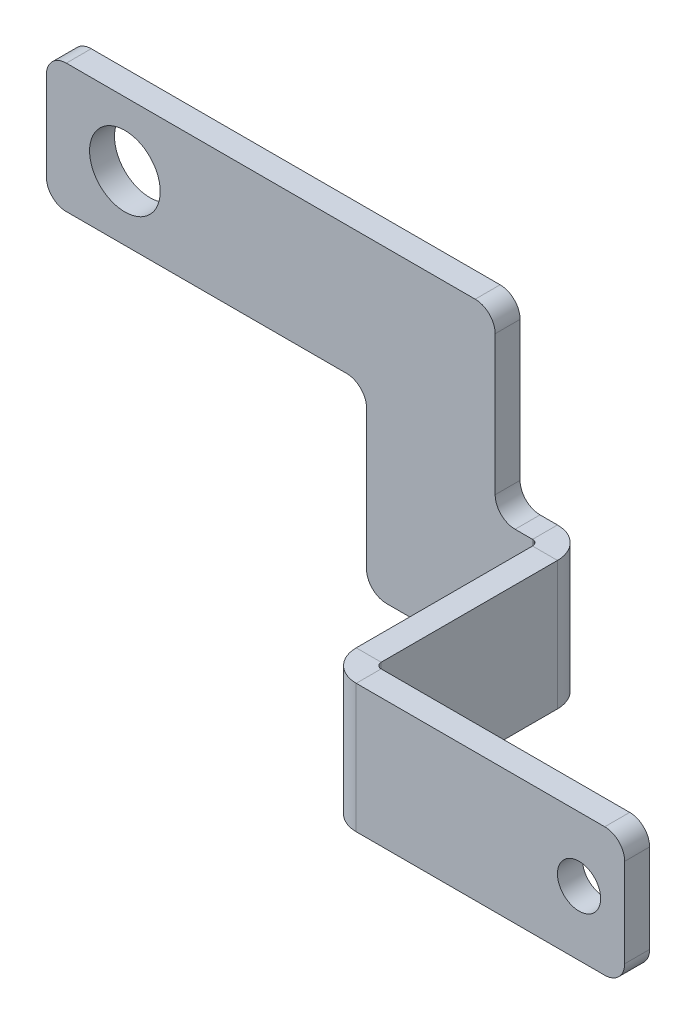
SolidWorks part; units mm, degrees
note: The reader was unsure of these and kept them because the rebuilt part matched: flange length of "Edge-Flange1", "Edge-Flange2".
material "3003-H14"
ref_plane "X-Y Datum" through (0, 0, 0) normal (0, 0, 1) x (1, 0, 0)
ref_plane "X-Z Datum" through (0, 0, 0) normal (0, 1, 0) x (1, 0, 0)
ref_plane "Y-Z Datum" through (0, 0, 0) normal (1, 0, 0) x (0, 0, -1)
sketch "Sketch1" plane through (0, 0, 0) normal (0, 0, 1) x (1, 0, 0)
  line L0 (0, -8.189) -> (57.15, -8.189) construction
  line L1 (0, 0) -> (57.15, 0)
  line L2 (0, 0) -> (0, -16.378)
  line L3 (0, -16.378) -> (40.772, -16.378)
  line L4 (57.15, 0) -> (57.15, -16.378)
  line L5 (61.9125, -31.0236) -> (56.0244, -31.0236) construction
  line L7 (57.15, -16.378) -> (57.15, -22.8346)
  line L8 (57.15, -39.2126) -> (40.772, -39.2126)
  line L9 (40.772, -16.378) -> (40.772, -39.2126)
  line L10 (57.15, -39.2126) -> (61.9125, -39.2126)
  line L12 (57.15, -22.8346) -> (61.9125, -22.8346)
  line L13 (61.9125, -39.2126) -> (61.9125, -22.8346)
  line L14 (88.5359, -31.0236) -> (101.3339, -31.0236) construction
  circle A0 centre (10, -8.189) radius 4 construction
  point P9 (94.9349, -31.0236)
  point P26 (94.9349, -31.0236)
  dimension "D3" = 8
  dimension "D1" = 16.378
  dimension "D2" = 57.15
  dimension "D4" = 10
  dimension "D5" = 4.7625
base flange "Base-Flange1" sketch "Sketch1" thickness 3.175 reverse thickness direction no parameters "D1"=0.7366
hole_wizard "M8 Clearance Hole1" positions "Sketch6" profile "Sketch7" hole size "M8" standard "ANSI Metric" end condition through all
sketch "Sketch6" plane through (0, 0, 0) normal (0, 0, 1) x (1, 0, 0)
  point P0 (10, -8.189)
sketch "Sketch7" plane through (10, -8.189, 0) normal (1, 0, 0) x (0, -1, 0)
  line L0 (0, 0) -> (0, 3.175)
  line L1 (0, 3.175) -> (4.5, 3.175)
  line L2 (4.5, 3.175) -> (4.5, 0)
  line L5 (4.5, 0) -> (0, 0)
  line L11 (0, -6.35) -> (0, 107.95) construction
  dimension "Thru Hole Dia." = 9
  dimension "Thru Hole Depth" = 3.175
edge flange "Edge-Flange1" sketch "Sketch12" flange angle 90 flange length 23.9268 flange position bend outside bend radius 0.7366 thickness 3.175 relief rectangular parameters "D6"=10
sketch "Sketch12" plane through (61.9125, 0, 0) normal (1, 0, 0) x (0, 1, 0)
  line L0 (-39.2126, 0) -> (-22.8346, 0) construction
  line L1 (-39.2126, 0) -> (-22.8346, 0)
  line L2 (-39.2126, 0) -> (-39.2126, 23.9268)
  line L3 (-39.2126, 23.9268) -> (-22.8346, 23.9268)
  line L4 (-22.8346, 23.9268) -> (-22.8346, 0)
bend "EdgeBend1" bend radius 0.7366 bend angle 90 parameters "D5"=1
edge flange "Edge-Flange2" sketch "Sketch15" flange angle 90 flange length 38.1 flange position material outside bend radius 0.7366 thickness 3.175 relief rectangular parameters "D6"=10
sketch "Sketch15" plane through (65.8241, 0, 23.9268) normal (0, 0, 1) x (0, -1, 0)
  line L0 (22.8346, 0) -> (39.2126, 0) construction
  line L1 (22.8346, 0) -> (39.2126, 0)
  line L2 (22.8346, 0) -> (22.8346, 34.925)
  line L3 (22.8346, 34.925) -> (39.2126, 34.925)
  line L4 (39.2126, 34.925) -> (39.2126, 0)
bend "EdgeBend2" bend radius 0.7366 bend angle 90 parameters "D5"=2
sketch "Sketch16" plane through (0, 0, 27.1018) normal (0, 0, 1) x (1, 0, 0)
  point P0 (94.9349, -31.0236)
hole_wizard "M5 Clearance Hole1" positions "Sketch17" profile "Sketch18" hole size "M5" standard "ANSI Metric" end condition through all
sketch "Sketch17" plane through (0, 0, 27.1018) normal (0, 0, 1) x (1, 0, 0)
  point P0 (94.9349, -31.0236)
  point P3 (94.9349, -31.0236)
  point P5 (94.9349, -31.0236)
sketch "Sketch18" plane through (94.9349, -31.0236, 27.1018) normal (1, 0, 0) x (0, -1, 0)
  line L0 (0, 0) -> (0, 30.2768)
  line L1 (0, 30.2768) -> (2.75, 30.2768)
  line L2 (2.75, 30.2768) -> (2.75, 0)
  line L5 (2.75, 0) -> (0, 0)
  line L11 (0, -6.35) -> (0, 107.95) construction
  dimension "Thru Hole Dia." = 5.5
  dimension "Thru Hole Depth" = 30.2768
fillet "Fillet1" radius 2.54 8 edges at (40.772, -16.378, -1.5875) (100.7491, -22.8346, 25.5143) (100.7491, -39.2126, 25.5143) (0, -16.378, -1.5875) (0, 0, -1.5875) (57.15, 0, -1.5875) (57.15, -22.8346, -1.5875) (40.772, -39.2126, -1.5875)
sketch "Bend-Lines1" [suppressed] plane through (0, 0, 0) normal (0, 1, 0) x (1, 0, 0)
sketch "Bounding-Box1" [suppressed] plane through (0, 0, 0) normal (0, 1, 0) x (1, 0, 0)
sheet metal parameters "Sheet-Metal3" thickness 3.175 parameters "D1"=0.7366
flat pattern "Flat-Pattern3" [suppressed]
sketch "Bend-Lines2" plane through (0, 0, 0) normal (0, 1, 0) x (1, 0, 0)
sketch3d "Bounding-Box2" [suppressed]
  line L0 (0, -16.378, 0) -> (-76.2, -16.378, 0) construction
  line L1 (0, 0, 0) -> (-76.2, 0, 0) construction
  line L2 (0, -16.378, 0) -> (0, 0, 0) construction
  line L3 (-76.2, -16.378, 0) -> (-76.2, 0, 0) construction
sheet metal parameters "Sheet-Metal4" thickness 3.175 parameters "D1"=0.7366
flat pattern "Flat-Pattern3"
sketch "Bend-Lines2" plane through (0, 0, 0) normal (0, 1, 0) x (1, 0, 0)
sketch3d "Bounding-Box2" [suppressed]
  line L0 (0, -16.378, 0) -> (76.2, -16.378, 0) construction
  line L1 (0, 0, 0) -> (76.2, 0, 0) construction
  line L2 (0, -16.378, 0) -> (0, 0, 0) construction
  line L3 (76.2, -16.378, 0) -> (76.2, 0, 0) construction
sheet metal parameters "Sheet-Metal5" thickness 3.175 parameters "D1"=0.7366
flat pattern "Flat-Pattern3"
sketch "Bend-Lines2" plane through (0, 0, 0) normal (0, 0, 1) x (1, 0, 0)
  line L0 (62.1503, -45.5626) -> (62.1503, -29.1846) construction
  line L1 (62.1503, -45.5626) -> (62.1503, -29.1846) construction
sketch3d "Bounding-Box2" [suppressed]
  line L0 (0, -45.5626, 0) -> (87.1659, -45.5626, 0) construction
  line L1 (0, 0, 0) -> (87.1659, 0, 0) construction
  line L2 (0, -45.5626, 0) -> (0, 0, 0) construction
  line L3 (87.1659, -45.5626, 0) -> (87.1659, 0, 0) construction
bend of the flat pattern "Flatten-<EdgeBend1>1"
sheet metal parameters "Sheet-Metal6" thickness 3.175 parameters "D1"=0.7366
flat pattern "Flat-Pattern3"
sketch "Bend-Lines2" plane through (0, 0, 0) normal (0, 0, 1) x (1, 0, 0)
  line L0 (62.1503, -45.5626) -> (62.1503, -29.1846) construction
  line L1 (62.1503, -45.5626) -> (62.1503, -29.1846) construction
  line L2 (88.2546, -45.5626) -> (88.2546, -29.1846) construction
  line L3 (88.2546, -45.5626) -> (88.2546, -29.1846) construction
sketch3d "Bounding-Box2" [suppressed]
  line L0 (0, -45.5626, 0) -> (125.5384, -45.5626, 0) construction
  line L1 (0, 0, 0) -> (125.5384, 0, 0) construction
  line L2 (0, -45.5626, 0) -> (0, 0, 0) construction
  line L3 (125.5384, -45.5626, 0) -> (125.5384, 0, 0) construction
bend of the flat pattern "Flatten-<EdgeBend1>1"
bend of the flat pattern "Flatten-<EdgeBend2>1"
sheet metal parameters "Sheet-Metal7" thickness 3.175 parameters "D1"=0.7366
flat pattern "Flat-Pattern3" [suppressed]
sketch "Bend-Lines2" plane through (0, 0, 0) normal (0, 0, 1) x (1, 0, 0)
  line L0 (63.7378, -39.2126) -> (63.7378, -22.8346) construction
  line L1 (63.7378, -39.2126) -> (63.7378, -22.8346) construction
  line L2 (89.8421, -39.2126) -> (89.8421, -22.8346) construction
  line L3 (89.8421, -39.2126) -> (89.8421, -22.8346) construction
sketch3d "Bounding-Box2" [suppressed]
  line L0 (0, -39.2126, 0) -> (125.8559, -39.2126, 0) construction
  line L1 (0, 0, 0) -> (125.8559, 0, 0) construction
  line L2 (0, -39.2126, 0) -> (0, 0, 0) construction
  line L3 (125.8559, -39.2126, 0) -> (125.8559, 0, 0) construction
bend of the flat pattern "Flatten-<EdgeBend1>1"
bend of the flat pattern "Flatten-<EdgeBend2>1"
sketch "Sketch16-1" plane through (25.1068, 0, 0) normal (0, 0, 1) x (1, 0, 0)
  point P0 (94.9349, -31.0236)
